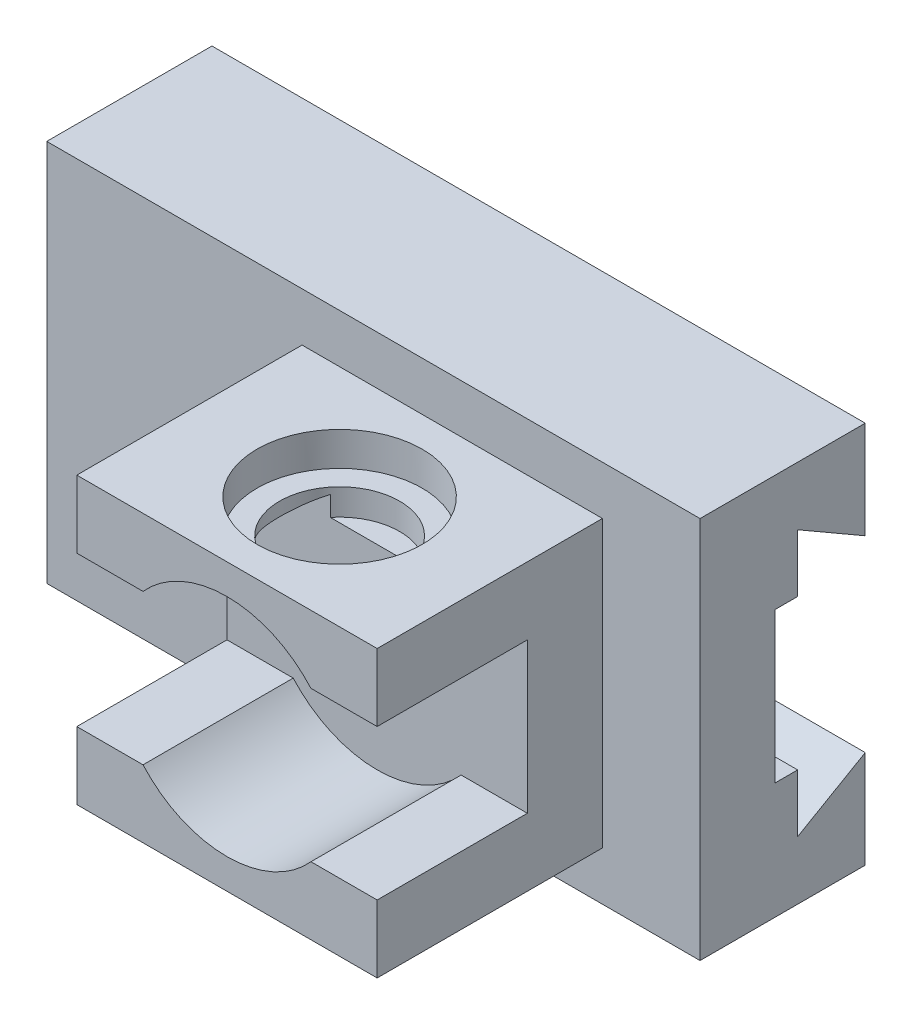
SolidWorks part; units mm, degrees
note: The reader was unsure of these and kept them because the rebuilt part matched: shared geometry of "Sketch2<5>".
ref_plane "Front Plane" through (0, 0, 0) normal (0, 0, 1) x (1, 0, 0)
ref_plane "Top Plane" through (0, 0, 0) normal (0, 1, 0) x (1, 0, 0)
ref_plane "Right Plane" through (0, 0, 0) normal (1, 0, 0) x (0, 0, -1)
sketch "Sketch1" plane through (0, 0, 0) normal (0, 0, 1) x (1, 0, 0)
  line L0 (0, 29.2968) -> (0, -38.6677) construction
  line L1 (-48.5899, 0) -> (49.2377, 0) construction
  line L2 (-43.5, 25.491) -> (-43.5, -25.491)
  line L3 (-43.5, -25.491) -> (43.5, -25.491)
  line L4 (43.5, -25.491) -> (43.5, 25.491)
  line L5 (43.5, 25.491) -> (-43.5, 25.491)
  dimension "lengthbox" = 87
  dimension "highbox" = 50.982
extrude "base-yellow" add sketch "Sketch1" against normal blind 22
ref_plane "Plane1" through (0, 0, 0) normal (0, 0, 1) x (1, 0, 0)
sketch "Sketch5" plane through (0, 0, 0) normal (0, 0, 1) x (1, 0, 0)
  line L0 (-58.6404, 0) -> (51.5993, 0) construction
  line L1 (0, 33.7865) -> (0, -36.0985) construction
  line L2 (-9.5, 19) -> (-9.5, -19)
  line L3 (-9.5, -19) -> (30.5, -19)
  line L4 (30.5, -19) -> (30.5, 19)
  line L5 (30.5, 19) -> (-9.5, 19)
  line L6 (-43.5, 25.491) -> (-43.5, -25.491) construction
  dimension "D1" = 38
  dimension "D2" = 40
  dimension "dist" = 34
extrude "base-red" add sketch "Sketch5" along normal blind 30
sketch "Sketch2" plane through (0, 19, -19) normal (0, -1, 0) x (1, 0, 0)
  line L0 (-55.6023, 19) -> (42.5138, 19) construction
  line L1 (30.5, 49) -> (30.5, 19) construction
  line L2 (0, -15.1747) -> (0, 77.8806) construction
  circle A0 centre (10.5, 34) radius 11
  circle A1 centre (10.5, 34) radius 8
  dimension "D1" = 22
  dimension "D2" = 16
  dimension "D3" = 20
  dimension "D4" = 15
sketch "Sketch8" plane through (-43.5, 0, 0) normal (-1, 0, 0) x (0, 0, 1)
  line L0 (-41.1874, 0) -> (36.1173, 0) construction
  line L1 (-10, 27.183) -> (-10, -35.8562) construction
  line L2 (0, 29.846) -> (0, -33.1932) construction
  line L3 (0, -28.0401) -> (0, 28.0401) construction
  line L4 (-10, 10) -> (-10, -10)
  line L5 (-10, -10) -> (-13, -10)
  line L6 (-10, 10) -> (-13, 10)
  line L7 (-13, -10) -> (-13, -17.6962)
  line L8 (-13, 10) -> (-13, 17.6962)
  line L9 (-13, -17.6962) -> (-22, -12.5)
  line L10 (-22, 25.491) -> (-22, -25.491) construction
  line L11 (-13, 17.6962) -> (-22, 12.5)
  line L12 (-22, 12.5) -> (-22, -12.5)
  dimension "D3" = 9
  dimension "D1" = 3
  dimension "D2" = 25
  dimension "D4" = 20
  dimension "angle" = 30
extrude "base-turkiz" cut sketch "Sketch8" against normal through all
extrude "counterbor" cut sketch "Sketch2" along normal blind 4.5 contours A0
sketch "Sketch7" plane through (0, 0, 30) normal (0, 0, 1) x (1, 0, 0)
  line L0 (0, 34.1018) -> (0, -39.0411) construction
  line L1 (52.8604, 0) -> (-64.4204, 0) construction
  line L2 (10.5, 16.6451) -> (10.5, -21.924) construction
  line L10 (-9.5, 19) -> (-9.5, -19) construction
  line L11 (-9.5, -10) -> (30.5, -10)
  line L12 (-9.5, -10) -> (-9.5, 10)
  line L13 (-9.5, 10) -> (30.5, 10)
  line L14 (30.5, -10) -> (30.5, 10)
  line L15 (30.5, -19) -> (30.5, 19) construction
  circle A0 centre (10.5, 0) radius 15
  dimension "D2" = 30
  dimension "D1" = 20
extrude "base-purple" cut sketch "Sketch7" against normal blind 20 contours L13 A0 | L11 A0
extrude "counterbor2" cut sketch "Sketch2<5>" along normal blind 8 contours A1 | A0
sketch "Sketch2<5>" plane through (0, 19, -19) normal (0, -1, 0) x (1, 0, 0) same geometry as "Sketch2"
equation "\"angle\"= 30"
equation "\"angle@Sketch8\"=\"angle\""
equation "\"dist\"= 34.00"
equation "\"counterbor\"= 0"
equation "\"counterbor2\"= 0"
equation "\"highbox@Sketch1\" = \"lengthbox@Sketch1\" * 0.586"
